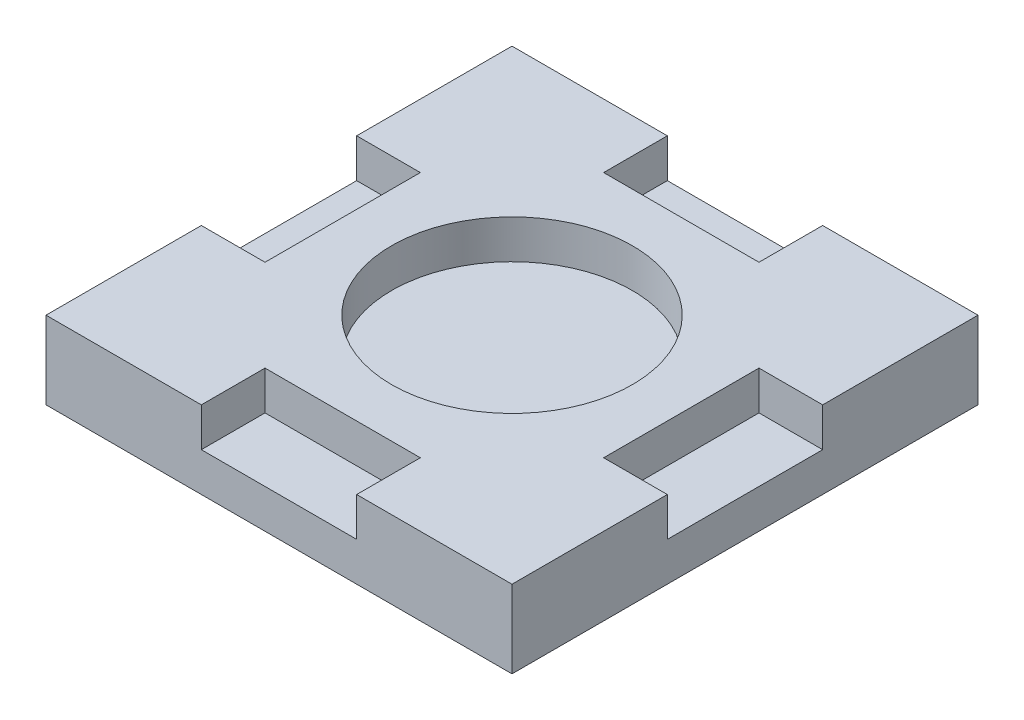
SolidWorks part; units mm, degrees
material "6061 Alloy"
ref_plane "Front Plane" through (0, 0, 0) normal (0, 0, 1) x (1, 0, 0)
ref_plane "Top Plane" through (0, 0, 0) normal (0, 1, 0) x (1, 0, 0)
ref_plane "Right Plane" through (0, 0, 0) normal (1, 0, 0) x (0, 0, -1)
sketch "Sketch1" plane through (0, 0, 0) normal (0, 1, 0) x (1, 0, 0)
  line L1 (0, 0) -> (76.2, 0)
  line L2 (0, 0) -> (0, 76.2)
  line L3 (0, 76.2) -> (76.2, 76.2)
  line L4 (76.2, 0) -> (76.2, 76.2)
  dimension "D1" = 76.2
  dimension "D2" = 76.2
extrude "Boss-Extrude1" add sketch "Sketch1" along normal blind 12.7
sketch "Sketch2" plane through (0, 12.7, 0) normal (0, 1, 0) x (1, 0, 0)
  line L0 (76.2, 76.2) -> (0, 76.2) construction
  line L1 (25.4, 76.2) -> (50.8, 76.2)
  line L2 (25.4, 76.2) -> (25.4, 65.786)
  line L3 (25.4, 65.786) -> (50.8, 65.786)
  line L4 (50.8, 76.2) -> (50.8, 65.786)
  line L5 (0, 76.2) -> (0, 0) construction
  line L6 (0, 50.8) -> (10.414, 50.8)
  line L7 (0, 50.8) -> (0, 25.4)
  line L8 (0, 25.4) -> (10.414, 25.4)
  line L9 (10.414, 50.8) -> (10.414, 25.4)
  line L10 (0, 0) -> (76.2, 0) construction
  line L11 (25.4, 0) -> (50.8, 0)
  line L12 (25.4, 0) -> (25.4, 10.414)
  line L13 (25.4, 10.414) -> (50.8, 10.414)
  line L14 (50.8, 0) -> (50.8, 10.414)
  line L15 (76.2, 0) -> (76.2, 76.2) construction
  line L16 (76.2, 50.8) -> (65.786, 50.8)
  line L17 (76.2, 50.8) -> (76.2, 25.4)
  line L18 (76.2, 25.4) -> (65.786, 25.4)
  line L19 (65.786, 50.8) -> (65.786, 25.4)
  dimension "D1" = 25.4
  dimension "D2" = 25.4
  dimension "D3" = 25.4
  dimension "D4" = 25.4
  dimension "D5" = 25.4
  dimension "D6" = 25.4
  dimension "D7" = 25.4
  dimension "D8" = 25.4
  dimension "D9" = 10.414
  dimension "D10" = 10.414
  dimension "D11" = 10.414
  dimension "D12" = 10.414
extrude "Cut-Extrude1" cut sketch "Sketch2" against normal blind 6.35
sketch "Sketch3" plane through (0, 12.7, 0) normal (0, 1, 0) x (1, 0, 0)
  line L0 (0, 50.8) -> (0, 25.4) construction
  line L1 (25.4, 0) -> (50.8, 0) construction
  circle A0 centre (38.1, 38.1) radius 19.685
  dimension "D1" = 39.37
  dimension "D2" = 38.1
  dimension "D3" = 38.1
extrude "Cut-Extrude2" cut sketch "Sketch3" against normal blind 6.35
